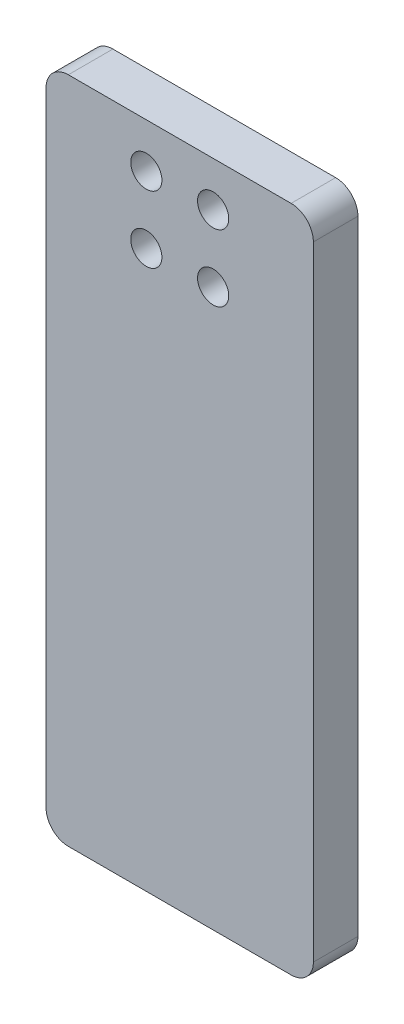
SolidWorks part; units mm, degrees
material "1.0038 (S235JRG2)"
ref_plane "Ön Düzlem" through (0, 0, 0) normal (0, 0, 1) x (1, 0, 0)
ref_plane "Üst Düzlem" through (0, 0, 0) normal (0, 1, 0) x (1, 0, 0)
ref_plane "Sağ Düzlem" through (0, 0, 0) normal (1, 0, 0) x (0, 0, -1)
sketch "Çizim1" plane through (0, 0, 0) normal (0, 0, 1) x (1, 0, 0)
  line L1 (-30, 75) -> (30, 75)
  line L2 (-30, 75) -> (-30, -75)
  line L3 (-30, -75) -> (30, -75)
  line L4 (30, 75) -> (30, -75)
  line L5 (-30, 75) -> (30, -75) construction
  line L6 (-30, -75) -> (30, 75) construction
  point P0 (0, 0)
  dimension "D1" = 150
  dimension "D2" = 60
base flange "Taban-Flanş1" sketch "Çizim1" thickness 10 reverse thickness direction no parameters "D1"=2
sketch "Çizim6" plane through (0, 0, 0) normal (0, 0, 1) x (1, 0, 0)
  line L0 (30, 75) -> (-30, 75) construction
  line L1 (-7.5, 65) -> (7.5, 65) construction
  line L2 (-7.5, 65) -> (-7.5, 50) construction
  line L3 (-7.5, 50) -> (7.5, 50) construction
  line L4 (7.5, 65) -> (7.5, 50) construction
  line L5 (-7.5, 65) -> (7.5, 50) construction
  line L6 (-7.5, 50) -> (7.5, 65) construction
  circle A0 centre (7.5, 65) radius 3.5
  circle A1 centre (-7.5, 65) radius 3.5
  circle A2 centre (7.5, 50) radius 3.5
  circle A3 centre (-7.5, 50) radius 3.5
  point P0 (0, 57.5)
  dimension "D1" = 7
  dimension "D2" = 15
  dimension "D3" = 15
  dimension "D4" = 10
extrude "Kes-Ekstrüzyon1" cut sketch "Çizim6" against normal blind 26
fillet "Radyus1" radius 5 4 edges at (-30, 75, -5) (30, 75, -5) (-30, -75, -5) (30, -75, -5)
sketch "Büküm-Çizgileri1" [suppressed] plane through (0, 0, 0) normal (0, 1, 0) x (1, 0, 0)
sketch "Sınırlandırma-Kutusu1" [suppressed] plane through (0, 0, 0) normal (0, 1, 0) x (1, 0, 0)
sheet metal parameters "Sac-Levha1" thickness 10 parameters "D1"=2
flat pattern "Düz-Çoğaltma1" [suppressed]
sketch "Büküm-Çizgileri2" plane through (0, 0, 0) normal (0, 1, 0) x (1, 0, 0)
sketch3d "Sınırlandırma-Kutusu2" [suppressed]
  line L0 (-50, 75, 0) -> (-50, -75, 0) construction
  line L1 (50, 75, 0) -> (50, -75, 0) construction
  line L2 (-50, 75, 0) -> (50, 75, 0) construction
  line L3 (-50, -75, 0) -> (50, -75, 0) construction
sheet metal parameters "Sac-Levha2" thickness 10 parameters "D1"=2
flat pattern "Düz-Çoğaltma1"
sketch "Büküm-Çizgileri2" plane through (0, 0, 0) normal (0, 1, 0) x (1, 0, 0)
sketch3d "Sınırlandırma-Kutusu2" [suppressed]
  line L0 (30, -75, 0) -> (30, 75, 0) construction
  line L1 (-30, -75, 0) -> (-30, 75, 0) construction
  line L2 (30, -75, 0) -> (-30, -75, 0) construction
  line L3 (30, 75, 0) -> (-30, 75, 0) construction
